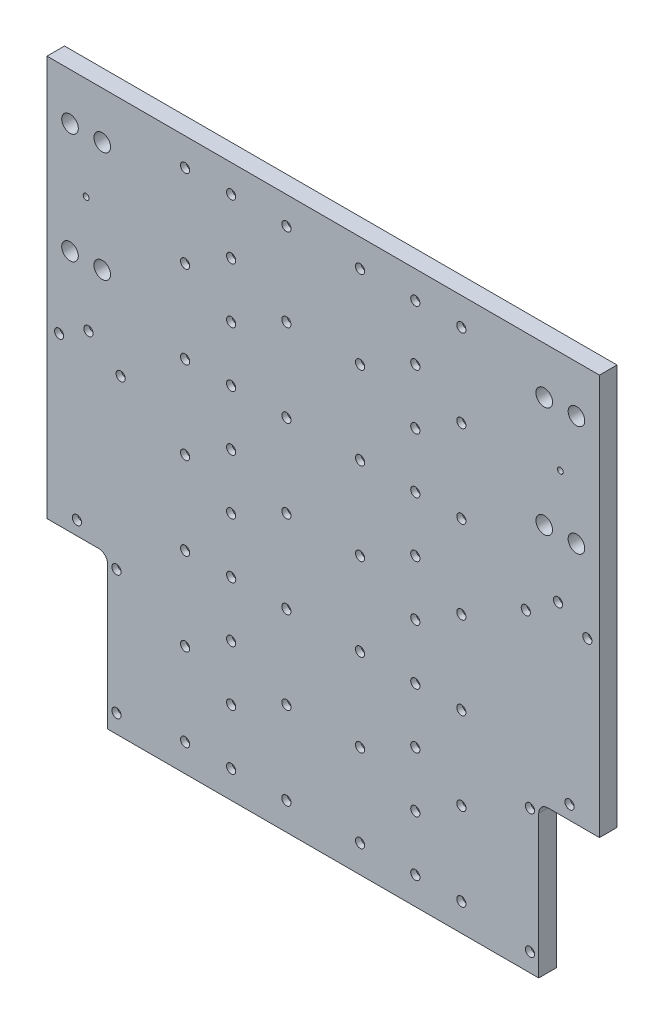
SolidWorks part; units mm, degrees
ref_plane "Front Plane" through (0, 0, 0) normal (0, 0, 1) x (1, 0, 0)
ref_plane "Top Plane" through (0, 0, 0) normal (0, 1, 0) x (1, 0, 0)
ref_plane "Right Plane" through (0, 0, 0) normal (1, 0, 0) x (0, 0, -1)
sketch "Sketch1" plane through (0, 0, 0) normal (0, 0, 1) x (1, 0, 0)
  line L1 (-300, 300) -> (300, 300)
  line L2 (-300, 300) -> (-300, -300)
  line L3 (-300, -300) -> (300, -300)
  line L4 (300, 300) -> (300, -300)
  dimension "D1" = 600
extrude "Boss-Extrude1" add sketch "Sketch1" along normal blind 19.05
sketch "Sketch2" plane through (0, 0, 0) normal (0, 0, -1) x (-1, 0, 0)
  line L0 (300, -300) -> (-300, -300) construction
  line L1 (300, 300) -> (300, -300) construction
  line L2 (234.05, -135) -> (300, -135) construction
  line L3 (234.05, -300) -> (234.05, -125) construction
  line L4 (-234.05, -125) -> (-234.05, -300) construction
  line L5 (-234.05, -135) -> (-300, -135) construction
  line L6 (300, -300) -> (234.05, -300)
  line L7 (300, -135) -> (300, -300)
  line L8 (234.05, -135) -> (300, -135)
  line L9 (234.05, -300) -> (234.05, -135)
  line L10 (-234.05, -135) -> (-234.05, -300)
  line L11 (-234.05, -135) -> (-300, -135)
  line L12 (-234.05, -300) -> (-300, -300)
  line L13 (-300, -135) -> (-300, -300)
extrude "Cut-Extrude1" cut sketch "Sketch2" against normal through all
fillet "Fillet1" radius 10 2 edges at (-234.05, -135, 9.525) (234.05, -135, 9.525)
sketch "Sketch5" plane through (0, 0, 0) normal (0, 0, -1) x (-1, 0, 0)
  circle A0 centre (240, 249) radius 9.017 construction
  circle A1 centre (275, 249) radius 9.017 construction
  circle A2 centre (257.5, 189) radius 3.175 construction
  circle A3 centre (275, 129) radius 9.017 construction
  circle A4 centre (240, 129) radius 9.017 construction
  circle A5 centre (-275, 129) radius 9.017 construction
  circle A6 centre (-240, 129) radius 9.017 construction
  circle A7 centre (-257.5, 189) radius 3.175 construction
  circle A8 centre (-275, 249) radius 9.017 construction
  circle A9 centre (-240, 249) radius 9.017 construction
  circle A10 centre (240, 249) radius 9.017
  circle A11 centre (275, 249) radius 9.017
  circle A12 centre (257.5, 189) radius 3.175
  circle A13 centre (275, 129) radius 9.017
  circle A14 centre (240, 129) radius 9.017
  circle A15 centre (-275, 129) radius 9.017
  circle A16 centre (-240, 129) radius 9.017
  circle A17 centre (-257.5, 189) radius 3.175
  circle A18 centre (-275, 249) radius 9.017
  circle A19 centre (-240, 249) radius 9.017
extrude "Cut-Extrude2" cut sketch "Sketch5" against normal through all
sketch "Sketch6" plane through (0, 0, 19.05) normal (0, 0, 1) x (1, 0, 0)
  line L0 (0, 0) -> (0, -72.3875)
  circle A0 centre (-150, -270) radius 2.5 construction
  circle A1 centre (-150, -180) radius 2.5 construction
  circle A2 centre (-150, -90) radius 2.5 construction
  circle A3 centre (-150, 0) radius 2.5 construction
  circle A4 centre (-150, 90) radius 2.5 construction
  circle A5 centre (-150, 180) radius 2.5 construction
  circle A6 centre (-150, 270) radius 2.5 construction
  circle A7 centre (150, 270) radius 2.5 construction
  circle A8 centre (150, 180) radius 2.5 construction
  circle A9 centre (150, 90) radius 2.5 construction
  circle A10 centre (150, 0) radius 2.5 construction
  circle A11 centre (150, -90) radius 2.5 construction
  circle A12 centre (150, -180) radius 2.5 construction
  circle A13 centre (150, -270) radius 2.5 construction
  circle A14 centre (-150, -270) radius 2.5
  circle A15 centre (-150, -180) radius 2.5
  circle A16 centre (-150, -90) radius 2.5
  circle A17 centre (-150, 0) radius 2.5
  circle A18 centre (-150, 90) radius 2.5
  circle A19 centre (-150, 180) radius 2.5
  circle A20 centre (-150, 270) radius 2.5
  circle A21 centre (150, 270) radius 2.5
  circle A22 centre (150, 180) radius 2.5
  circle A23 centre (150, 90) radius 2.5
  circle A24 centre (150, 0) radius 2.5
  circle A25 centre (150, -90) radius 2.5
  circle A26 centre (150, -180) radius 2.5
  circle A27 centre (150, -270) radius 2.5
  circle A28 centre (40, 270) radius 2.5
  circle A29 centre (40, 180) radius 2.5
  circle A30 centre (40, 0) radius 2.5
  circle A31 centre (40, -90) radius 2.5
  circle A32 centre (40, -180) radius 2.5
  circle A33 centre (40, 90) radius 2.5
  circle A34 centre (40, -270) radius 2.5
  circle A35 centre (-40, -270) radius 2.5
  circle A36 centre (-40, 90) radius 2.5
  circle A37 centre (-40, -180) radius 2.5
  circle A38 centre (-40, -90) radius 2.5
  circle A39 centre (-40, 0) radius 2.5
  circle A40 centre (-40, 180) radius 2.5
  circle A41 centre (-40, 270) radius 2.5
sketch "Sketch7" plane through (0, 0, 19.05) normal (0, 0, 1) x (1, 0, 0)
  line L16 (0, -65.4775) -> (0, 65.4775) construction
  line L17 (215, -48.8) -> (215, -44.1371) construction
  line L18 (238.4315, 12.4315) -> (300, 74) construction
  line L19 (300, 74) -> (300, 45.7157) construction
  line L20 (300, 45.7157) -> (252.5736, -1.7107) construction
  line L21 (235, -44.1371) -> (300, -44.1371) construction
  line L22 (300, -44.1371) -> (300, -48.8) construction
  line L24 (300, -48.8) -> (300, -64.1371) construction
  line L25 (300, -64.1371) -> (235, -64.1371) construction
  line L26 (235, -64.1371) -> (235, -105) construction
  line L27 (235, -105) -> (300, -105) construction
  line L28 (300, -105) -> (300, -135) construction
  line L29 (300, -135) -> (234.05, -135) construction
  line L30 (234.05, -135) -> (234.05, -125) construction
  line L31 (234.05, -125) -> (215, -125) construction
  line L32 (215, -125) -> (215, -48.8) construction
  line L34 (-300, -64.1371) -> (-300, -48.8) construction
  line L36 (-215, -48.8) -> (-215, -125) construction
  line L37 (-215, -125) -> (-234.05, -125) construction
  line L38 (-234.05, -125) -> (-234.05, -135) construction
  line L39 (-234.05, -135) -> (-300, -135) construction
  line L40 (-300, -135) -> (-300, -105) construction
  line L41 (-300, -105) -> (-235, -105) construction
  line L42 (-235, -105) -> (-235, -64.1371) construction
  line L43 (-235, -64.1371) -> (-300, -64.1371) construction
  line L44 (-215, -44.1371) -> (-215, -48.8) construction
  line L46 (-300, -48.8) -> (-300, -44.1371) construction
  line L47 (-300, -44.1371) -> (-235, -44.1371) construction
  line L48 (-252.5736, -1.7107) -> (-300, 45.7157) construction
  line L49 (-300, 45.7157) -> (-300, 74) construction
  line L50 (-300, 74) -> (-238.4315, 12.4315) construction
  line L51 (215, -48.8) -> (215, -44.1371)
  line L52 (238.4315, 12.4315) -> (300, 74)
  line L53 (300, 74) -> (300, 45.7157)
  line L54 (300, 45.7157) -> (252.5736, -1.7107)
  line L55 (235, -44.1371) -> (300, -44.1371)
  line L56 (300, -44.1371) -> (300, -48.8)
  line L58 (300, -48.8) -> (300, -64.1371)
  line L59 (300, -64.1371) -> (235, -64.1371)
  line L60 (235, -64.1371) -> (235, -105)
  line L61 (235, -105) -> (300, -105)
  line L62 (300, -105) -> (300, -135)
  line L63 (300, -135) -> (234.05, -135)
  line L64 (234.05, -135) -> (234.05, -125)
  line L65 (234.05, -125) -> (215, -125)
  line L66 (215, -125) -> (215, -48.8)
  line L68 (-300, -64.1371) -> (-300, -48.8)
  line L70 (-215, -48.8) -> (-215, -125)
  line L71 (-215, -125) -> (-234.05, -125)
  line L72 (-234.05, -125) -> (-234.05, -135)
  line L73 (-234.05, -135) -> (-300, -135)
  line L74 (-300, -135) -> (-300, -105)
  line L75 (-300, -105) -> (-235, -105)
  line L76 (-235, -105) -> (-235, -64.1371)
  line L77 (-235, -64.1371) -> (-300, -64.1371)
  line L78 (-215, -44.1371) -> (-215, -48.8)
  line L80 (-300, -48.8) -> (-300, -44.1371)
  line L81 (-300, -44.1371) -> (-235, -44.1371)
  line L82 (-252.5736, -1.7107) -> (-300, 45.7157)
  line L83 (-300, 45.7157) -> (-300, 74)
  line L84 (-300, 74) -> (-238.4315, 12.4315)
  circle A0 centre (224.525, -145) radius 2.5
  circle A1 centre (224.525, -280) radius 2.5
  circle A2 centre (-224.525, -145) radius 2.5
  circle A3 centre (-224.525, -280) radius 2.5
  arc A4 (238.4315, 12.4315) -> (215, -44.1371) centre (295, -44.1371) ccw construction
  arc A5 (252.5736, -1.7107) -> (235, -44.1371) centre (295, -44.1371) ccw construction
  arc A6 (-235, -44.1371) -> (-252.5736, -1.7107) centre (-295, -44.1371) ccw construction
  arc A7 (-215, -44.1371) -> (-238.4315, 12.4315) centre (-295, -44.1371) ccw construction
  arc A8 (238.4315, 12.4315) -> (215, -44.1371) centre (295, -44.1371) ccw
  arc A9 (252.5736, -1.7107) -> (235, -44.1371) centre (295, -44.1371) ccw
  arc A10 (-235, -44.1371) -> (-252.5736, -1.7107) centre (-295, -44.1371) ccw
  arc A11 (-215, -44.1371) -> (-238.4315, 12.4315) centre (-295, -44.1371) ccw
  circle A14 centre (286.8234, 45.7157) radius 2.5
  circle A15 centre (267.5, -120) radius 2.5
  circle A16 centre (-267.5, -120) radius 2.5
  circle A17 centre (-286.8234, 45.7157) radius 2.5
hole_wizard "CBORE for M5 SHCS1" positions "Sketch3" profile "Sketch4" counterbore size "M5" standard "ANSI Metric"
sketch "Sketch3" plane through (0, 0, 19.05) normal (0, 0, 1) x (1, 0, 0)
  point P0 (-100, 210)
  point P3 (-100, 270)
  point P6 (100, 270)
  point P9 (100, 210)
  point P12 (100, 150)
  point P15 (-100, 150)
  point P18 (-100, 90)
  point P21 (100, 90)
  point P24 (100, 30)
  point P27 (-100, 30)
  point P30 (-255, 64)
  point P33 (-220, 39)
  point P36 (255, 64)
  point P39 (220, 39)
  point P42 (100, -30)
  point P45 (-100, -30)
  point P48 (-100, -90)
  point P51 (100, -90)
  point P54 (100, -150)
  point P57 (-100, -150)
  point P60 (-100, -210)
  point P63 (100, -210)
  point P66 (100, -270)
  point P69 (-100, -270)
  point P72 (150, -270)
  point P75 (150, -180)
  point P78 (150, -90)
  point P81 (150, 0)
  point P84 (150, 90)
  point P87 (150, 180)
  point P90 (150, 270)
  point P93 (40, 270)
  point P96 (40, 180)
  point P99 (-40, 180)
  point P102 (-40, 270)
  point P105 (-150, 270)
  point P108 (-150, 180)
  point P111 (-150, 90)
  point P114 (-40, 90)
  point P117 (40, 90)
  point P120 (40, 0)
  point P123 (-40, 0)
  point P126 (-40, -90)
  point P129 (40, -90)
  point P132 (-150, -90)
  point P135 (-150, 0)
  point P138 (-150, -90)
  point P141 (-150, 0)
  point P143 (-220, 39)
  point P145 (-255, 64)
  point P147 (-150, -90)
  point P149 (-150, -180)
  point P152 (-150, -270)
  point P155 (-40, -270)
  point P158 (-40, -180)
  point P161 (40, -180)
  point P164 (40, -270)
  point P167 (224.525, -280)
  point P170 (224.525, -145)
  point P173 (-224.525, -145)
  point P176 (-224.525, -280)
  point P179 (-267.5, -120)
  point P182 (-286.8234, 45.7157)
  point P185 (286.8234, 45.7157)
  point P188 (267.5, -120)
sketch "Sketch4" plane through (-100, 210, 19.05) normal (1, 0, 0) x (0, -1, 0)
  line L0 (0, 0) -> (0, 30)
  line L1 (0, 30) -> (2.75, 28.3476)
  line L2 (2.75, 28.3476) -> (2.75, 6)
  line L3 (2.75, 6) -> (5, 6)
  line L4 (5, 6) -> (5, 0)
  line L5 (5, 0) -> (0, 0)
  line L10 (0, 30) -> (-2.75, 28.3476) construction
  line L11 (0, -6.35) -> (0, 107.95) construction
  dimension "Hole Dia." = 5.5
  dimension "Hole Depth" = 30
  dimension "C'Bore Dia." = 10
  dimension "C'Bore Depth" = 6
  dimension "Drill Angle" = 118
